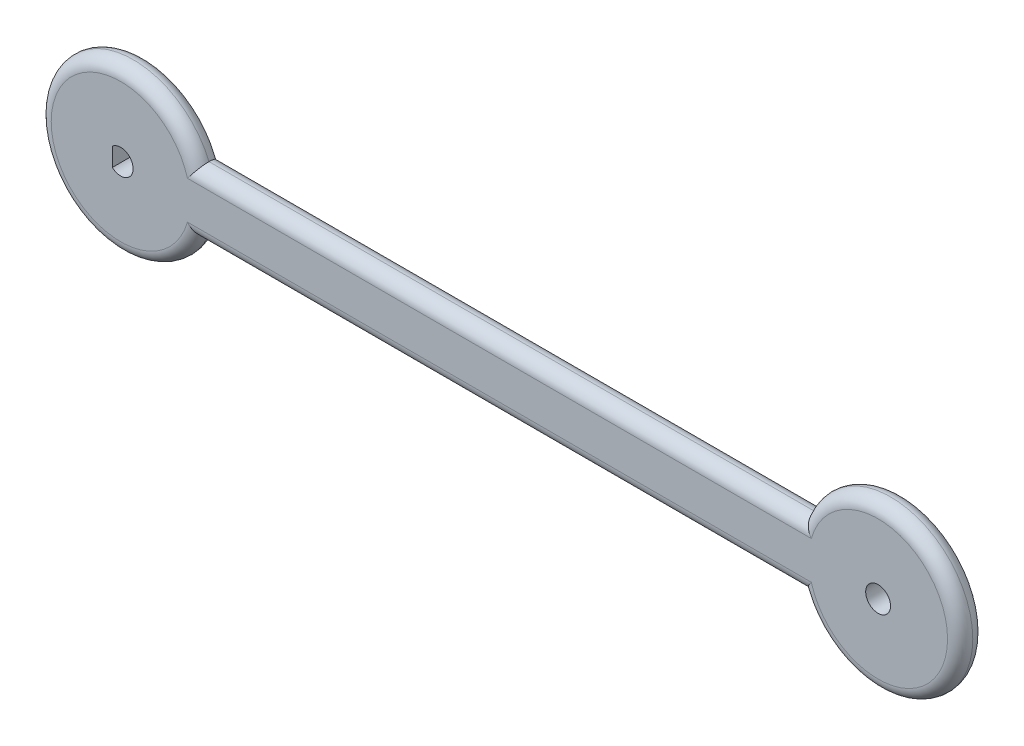
SolidWorks part; units mm, degrees
ref_plane "Front Plane" through (0, 0, 0) normal (0, 0, 1) x (1, 0, 0)
ref_plane "Top Plane" through (0, 0, 0) normal (0, 1, 0) x (1, 0, 0)
ref_plane "Right Plane" through (0, 0, 0) normal (1, 0, 0) x (0, 0, -1)
sketch "Sketch1" plane through (0, 0, 0) normal (0, 0, 1) x (1, 0, 0)
  line L0 (-1.6783, 1.8555) -> (-1.6783, -1.8555)
  line L1 (15.24, -6.35) -> (137.16, -6.35)
  line L2 (15.24, 6.35) -> (137.16, 6.35)
  arc A0 (-1.6783, -1.8555) -> (-1.6783, 1.8555) centre (0, 0) ccw
  arc A1 (15.24, 6.35) -> (15.24, -6.35) centre (0, 0) ccw
  circle A2 centre (152.4, 0) radius 2.5019
  arc A3 (137.16, -6.35) -> (137.16, 6.35) centre (152.4, 0) ccw
  point P8 (0, 0)
  point P9 (0, 0)
  dimension "D1" = 5.0038
  dimension "D2" = 33.02
  dimension "D4" = 33.02
  dimension "D5" = 5.0038
  dimension "D3" = 152.4
  dimension "D6" = 3.711
extrude "Boss-Extrude1" add sketch "Sketch1" along normal blind 5.08
fillet "Fillet1" radius 2.54 4 edges at (-16.51, 0, 5.08) (76.2, -6.35, 5.08) (76.2, 6.35, 5.08) (168.91, 0, 5.08)
fillet "Fillet2" radius 2.54 4 edges at (76.2, -6.35, 0) (-16.51, 0, 0) (76.2, 6.35, 0) (168.91, 0, 0)
